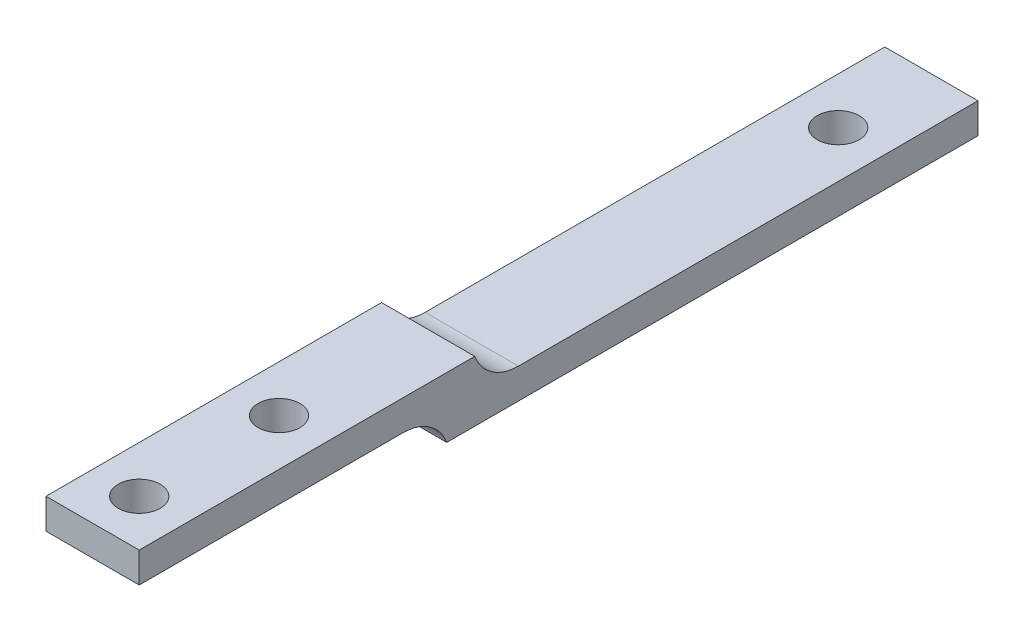
SolidWorks part; units mm, degrees
ref_plane "Front Plane" through (0, 0, 0) normal (0, 0, 1) x (1, 0, 0)
ref_plane "Top Plane" through (0, 0, 0) normal (0, 1, 0) x (1, 0, 0)
ref_plane "Right Plane" through (0, 0, 0) normal (1, 0, 0) x (0, 0, -1)
sketch "Sketch1" plane through (0, 0, 0) normal (0, 1, 0) x (1, 0, 0)
  line L0 (0, 0) -> (0, 90) construction
  line L1 (0, 0) -> (-5, 0)
  line L2 (-5, 0) -> (-5, 90)
  line L3 (-5, 90) -> (5, 90)
  line L4 (5, 90) -> (5, 0)
  line L5 (5, 0) -> (0, 0)
  circle A0 centre (0, 20) radius 2.25
  circle A1 centre (0, 5) radius 2.25
  circle A2 centre (0, 80) radius 2.25
  dimension "D1" = 4.5
  dimension "D2" = 10
  dimension "D3" = 15
  dimension "D4" = 5
  dimension "D5" = 10
  dimension "D6" = 60
extrude "Boss-Extrude1" add sketch "Sketch1" along normal blind 6.5
sketch "Sketch2" plane through (0, 0, 0) normal (1, 0, 0) x (0, 0, -1)
  line L0 (0, 3.25) -> (90, 3.25) construction
  line L1 (0, 6.5) -> (0, 0) construction
  line L2 (90, 6.5) -> (90, 0) construction
  line L3 (30, 6.5) -> (30, 0) construction
  line L4 (0, 6.5) -> (90, 6.5) construction
  line L5 (0, 0) -> (90, 0) construction
  line L6 (5, 6.5) -> (5, 0) construction
  line L8 (20, 6.5) -> (20, 0) construction
  line L9 (0, 3.25) -> (33, 3.25)
  line L10 (0, 3.25) -> (0, 0)
  line L11 (0, 0) -> (33, 0)
  line L12 (33, 3.25) -> (33, 0)
  line L13 (90, 6.5) -> (36, 6.5)
  line L14 (90, 6.5) -> (90, 3.25)
  line L15 (90, 3.25) -> (36, 3.25)
  line L16 (36, 6.5) -> (36, 3.25)
  dimension "D1" = 5
  dimension "D2" = 15
  dimension "D3" = 10
  dimension "D4" = 30
  dimension "D5" = 3
  dimension "D6" = 3
extrude "Cut-Extrude1" cut sketch "Sketch2" against normal blind 5 and the other way blind 5
fillet "Fillet1" radius 5 2 edges at (0, 3.25, -33) (0, 3.25, -36)
